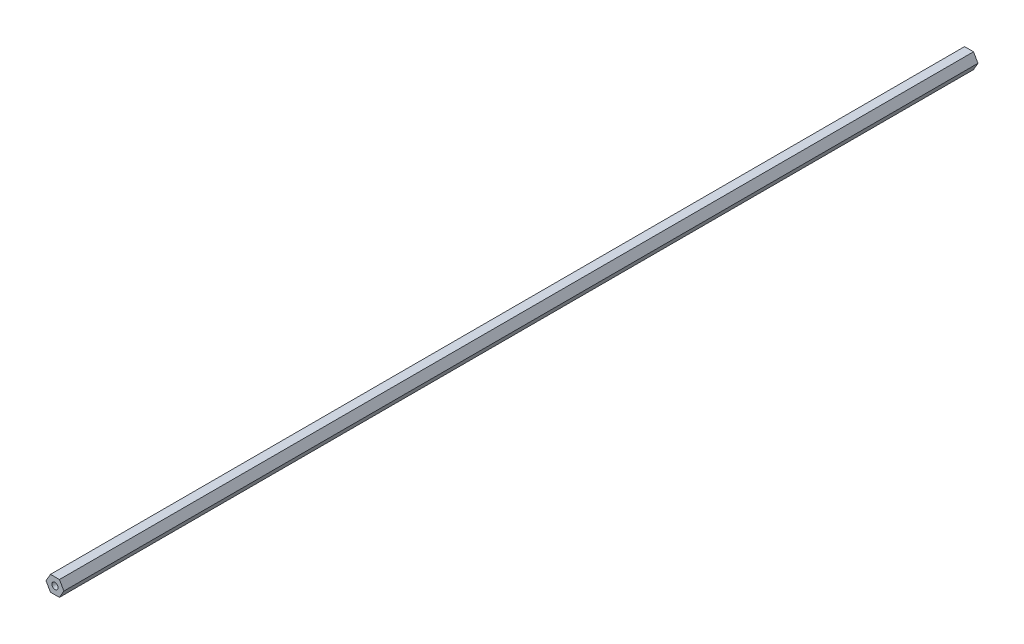
SolidWorks part; units mm, degrees
ref_plane "Front Plane" through (0, 0, 0) normal (0, 0, 1) x (1, 0, 0)
ref_plane "Top Plane" through (0, 0, 0) normal (0, 1, 0) x (1, 0, 0)
ref_plane "Right Plane" through (0, 0, 0) normal (1, 0, 0) x (0, 0, -1)
sketch "Sketch1" plane through (0, 0, 0) normal (0, 0, 1) x (1, 0, 0)
  line L1 (3.6662, -6.35) -> (7.3323, 0)
  line L2 (7.3323, 0) -> (3.6662, 6.35)
  line L3 (3.6662, 6.35) -> (-3.6662, 6.35)
  line L4 (-3.6662, 6.35) -> (-7.3323, 0)
  line L5 (-7.3323, 0) -> (-3.6662, -6.35)
  line L6 (-3.6662, -6.35) -> (3.6662, -6.35)
  circle A0 centre (0, 0) radius 6.35 construction
  circle A1 centre (0, 0) radius 2.5527
  dimension "D1" = 5.1054
  dimension "D2" = 12.7
extrude "Boss-Extrude1" add sketch "Sketch1" along normal blind 749.3
